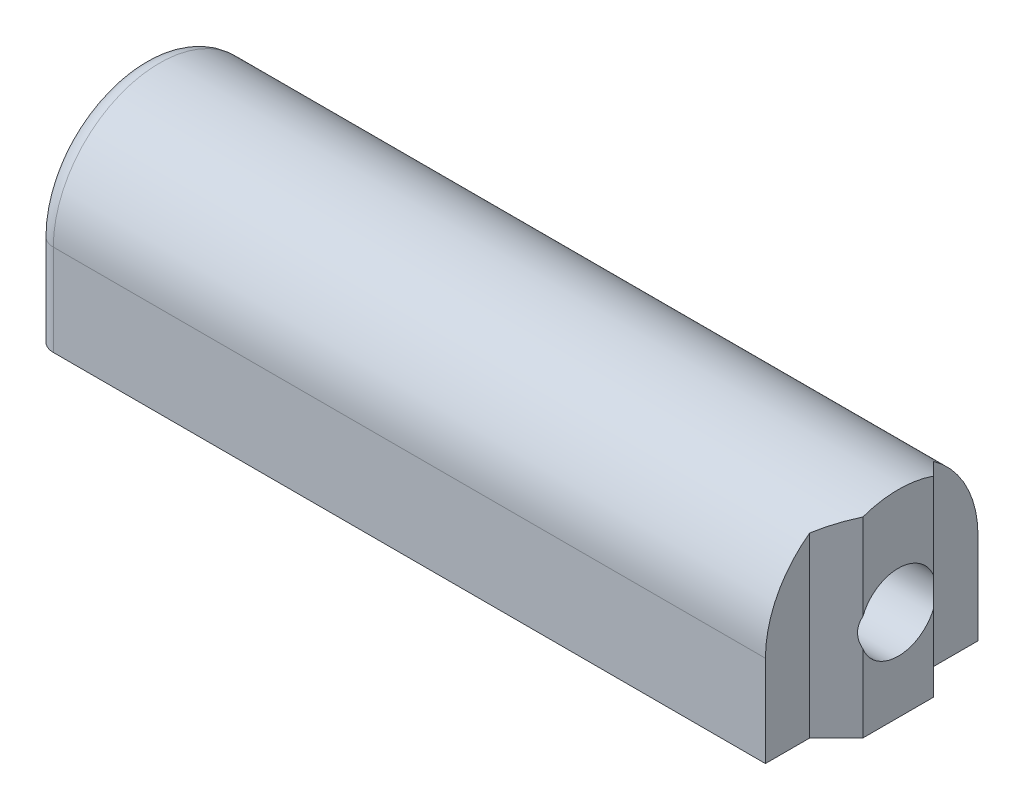
SolidWorks part; units mm, degrees
material "Custom Plastic"
ref_plane "Front Plane" through (0, 0, 0) normal (0, 0, 1) x (1, 0, 0)
ref_plane "Top Plane" through (0, 0, 0) normal (0, 1, 0) x (1, 0, 0)
ref_plane "Right Plane" through (0, 0, 0) normal (1, 0, 0) x (0, 0, -1)
sketch "Sketch1" plane through (0, 0, 0) normal (0, 0, 1) x (1, 0, 0)
  line L0 (0, 0) -> (41.2, 0)
  line L8 (0, 0) -> (0, 13)
  line L9 (0, 13) -> (41.2, 13)
  line L10 (41.2, 0) -> (41.2, 13)
  dimension "D1" = 41.2
  dimension "D5" = 13
extrude "Boss-Extrude1" add sketch "Sketch1" along normal blind 12
sketch "Sketch3" plane through (0, 13, 0) normal (0, 1, 0) x (1, 0, 0)
  line L0 (41.2, -12) -> (41.2, 0) construction
  line L1 (42.7, -8) -> (41.2, -9.5)
  line L2 (42.7, -8) -> (42.7, -4)
  line L3 (42.7, -4) -> (41.2, -2.5)
  line L4 (41.2, -9.5) -> (41.2, -2.5)
  line L7 (42.7, -6) -> (41.2, -6) construction
  point P0 (26.8, -6)
  dimension "D1" = 7
  dimension "D2" = 4
  dimension "D3" = 1.5
extrude "Boss-Extrude3" add sketch "Sketch3" against normal up to surface (13 mm away) up to face at (20.6, 0, 6)
sketch "Sketch2" plane through (0, 0, 0) normal (-1, 0, 0) x (0, 0, 1)
  line L0 (0, 3) -> (12, 3) construction
  line L1 (0, 13) -> (0, 0) construction
  line L2 (12, 13) -> (12, 0) construction
  line L4 (6, 5.15) -> (6, 13) construction
  line L5 (12, 13) -> (0, 13) construction
  line L8 (-1.8981, 5.15) -> (0, 5.15)
  line L9 (-1.8981, 14.3189) -> (16.1982, 14.3189)
  line L10 (-1.8981, 14.3189) -> (-1.8981, 5.15)
  line L12 (16.1982, 14.3189) -> (16.1982, 5.15)
  line L13 (12, 5.15) -> (16.1982, 5.15)
  circle A0 centre (6, 5.15) radius 2.15
  arc A1 (12, 5.15) -> (0, 5.15) centre (6, 5.15) ccw
  dimension "D2" = 4.3
extrude "Cut-Extrude1" cut sketch "Sketch2" against normal through all
fillet "Fillet1" radius 1 3 edges at (0, 2.575, 0) (0, 2.575, 12) (0, 11.15, 6)
equation "\"y-cross-rib-thickness\"=6"
equation "\"y-rib-thickness\"=6"
equation "\"bed-plate-thickness\"=6"
equation "\"x-plate-thickness\"=5"
equation "\"rod-diameter\"=12"
equation "\"t-nut-hole-diameter\"=3"
equation "\"y-plate-thickness\"=5"
equation "\"enclosure-thickness\"=0.6"
equation "\"M3-Clearance\"=3.3"
equation "\"M4-Clearance\"=4.3"
equation "\"M5-Clearance\"=5.3"
equation "\"M6-Clearance\"=6.3"
equation "\"M8-Clearance\"=8.3"
equation "\"623-Bearing-Dia\"=11.2"
